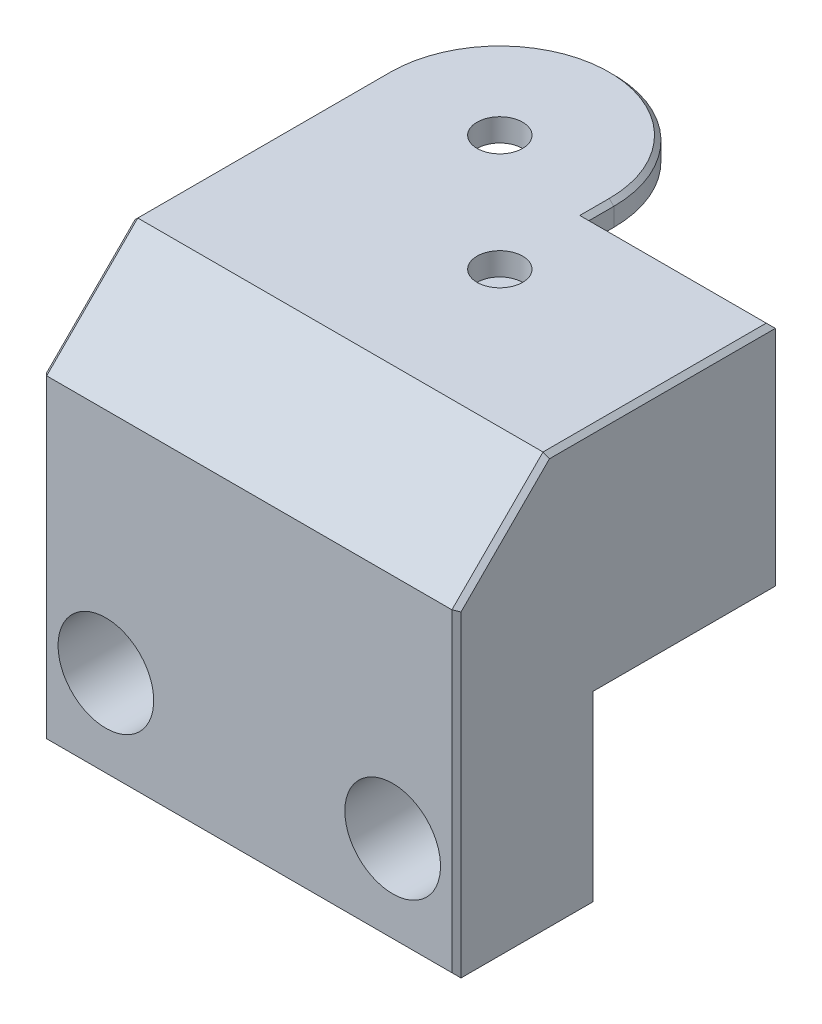
SolidWorks part; units mm, degrees
ref_plane "Front Plane" through (0, 0, 0) normal (0, 0, 1) x (1, 0, 0)
ref_plane "Top Plane" through (0, 0, 0) normal (0, 1, 0) x (1, 0, 0)
ref_plane "Right Plane" through (0, 0, 0) normal (1, 0, 0) x (0, 0, -1)
sketch "Sketch1" plane through (0, 0, 0) normal (0, 1, 0) x (1, 0, 0)
  line L0 (0, 0) -> (-20.24, 0) construction
  line L1 (20.24, -10) -> (25.24, -10)
  line L2 (-20.24, 10) -> (20.24, 10)
  line L3 (-20.24, 10) -> (-20.24, -10)
  line L4 (-20.24, -10) -> (20.24, -10)
  line L5 (20.24, 10) -> (20.24, -10) construction
  line L6 (-20.24, 10) -> (20.24, -10) construction
  line L7 (-20.24, -10) -> (20.24, 10) construction
  line L8 (25.24, -10) -> (25.24, 10)
  line L9 (25.24, 10) -> (20.24, 10)
  circle A0 centre (0, 0) radius 2.5
  point P3 (0, 0)
  dimension "D1" = 5
  dimension "D2" = 20
  dimension "D3" = 20.24
  dimension "D4" = 5
extrude "Boss-Extrude1" add sketch "Sketch1" along normal blind 25
sketch "Sketch9" plane through (0, 0, 10) normal (0, 0, 1) x (1, 0, 0)
  line L0 (25.24, 25) -> (25.24, 0) construction
  line L1 (-20.24, 25) -> (25.24, 25)
  line L2 (-20.24, 25) -> (-20.24, -20)
  line L3 (-20.24, -20) -> (25.24, -20)
  line L4 (25.24, 25) -> (25.24, -20)
  line L6 (-20.24, 0) -> (25.24, 0) construction
  dimension "D1" = 20
extrude "Boss-Extrude4" add sketch "Sketch9" along normal blind 15
sketch "Sketch10" plane through (0, 25, 0) normal (0, 1, 0) x (1, 0, 0)
  line L0 (10.16, 0) -> (10.16, 10)
  line L1 (25.24, 10) -> (-20.24, 10) construction
  line L2 (10.16, 10) -> (-10.16, 10)
  line L3 (-10.16, 10) -> (-10.16, 0)
  arc A0 (10.16, 0) -> (-10.16, 0) centre (0, 0) cw
  dimension "D1" = 10.16
extrude "Cut-Extrude2" cut sketch "Sketch10" against normal blind 19.5 from offset 2.5 offset against normal yes
sketch "Sketch14" plane through (0, 25, 0) normal (0, 1, 0) x (1, 0, 0)
  line L0 (464.5276, -6.3662) -> (0, -6.3662) construction
  line L1 (48.7314, 6.3662) -> (12.7324, 6.3662) construction
  line L2 (464.5276, -6.3662) -> (0, -6.3662)
  line L3 (48.7314, 6.3662) -> (12.7324, 6.3662)
  circle A0 centre (12.7324, 12.7324) radius 9.017 construction
  circle A1 centre (12.7324, 12.7324) radius 9.017
sketch "Sketch15" plane through (0, 25, 0) normal (0, 1, 0) x (1, 0, 0)
  line L0 (25.24, 10) -> (25.24, 12.7324)
  line L1 (0.2248, 12.7324) -> (0.2248, 10)
  line L2 (0.2248, 10) -> (25.24, 10)
  arc A0 (25.24, 12.7324) -> (0.2248, 12.7324) centre (12.7324, 12.7324) ccw
  circle A1 centre (12.7324, 12.7324) radius 2.5
  dimension "D1" = 5
extrude "Boss-Extrude5" add sketch "Sketch15" against normal up to surface (25 mm away) up to face at (2.5, 0, 0)
chamfer "Chamfer1" distance 10 angle 45 1 edges at (2.5, 25, 25)
ref_axis "Axis1" through (0, 3, 0) along (0, -1, 0)
ref_plane "Plane1" through (0, 0, 0) normal (-1, 0, 0) x (0, 0, 1)
sketch "Sketch16" plane through (25.24, 0, 0) normal (1, 0, 0) x (0, 0, -1)
  line L0 (-10.16, 22.5) -> (-10.16, 3) construction
  line L1 (-10.16, 3) -> (29.84, 3)
  line L2 (-10.16, 3) -> (-10.16, 22.5)
  line L3 (-10.16, 22.5) -> (29.84, 22.5)
  line L4 (29.84, 3) -> (29.84, 22.5)
  line L5 (2.5, 3) -> (-2.5, 3) construction
  line L6 (-2.5, 22.5) -> (2.5, 22.5) construction
  dimension "D1" = 40
extrude "Cut-Extrude3" cut sketch "Sketch16" against normal up to surface (25.24 mm away) up to plane "Plane1"
sketch "Sketch11" plane through (0, 0, 25) normal (0, 0, 1) x (1, 0, 0)
  line L0 (-20.24, -10) -> (25.24, -10) construction
  line L1 (25.24, -20) -> (25.24, 15) construction
  line L2 (-20.24, 15) -> (-20.24, -20) construction
  line L3 (-20.24, -20) -> (25.24, -20) construction
  circle A0 centre (-13.24, -10) radius 7
  circle A1 centre (18.24, -10) radius 7
  dimension "D2" = 14
  dimension "D1" = 10
sketch "Sketch17" plane through (0, 25, 0) normal (0, 1, 0) x (1, 0, 0)
  line L0 (0, 0) -> (10.16, 0) construction
  line L1 (10.16, 0) -> (25.24, 0) construction
  line L2 (25.24, -10.16) -> (25.24, 12.7324) construction
  line L3 (10.16, -3) -> (25.24, -3)
  line L4 (10.16, 3) -> (25.24, 3)
  line L5 (10.16, -3) -> (10.16, 3)
  line L6 (25.24, -3) -> (25.24, 3)
  dimension "D1" = 10.16
  dimension "D2" = 3
  dimension "D3" = 3
extrude "Boss-Extrude6" add sketch "Sketch17" against normal up to surface (22 mm away) up to face at (0, 3, -2.5)
hole_wizard "CBORE for M5 SBHCS1" positions "Sketch12" profile "Sketch13" counterbore size "M5" standard "ANSI Metric" end condition through all
sketch "Sketch12" plane through (0, 0, 25) normal (0, 0, 1) x (1, 0, 0)
  point P0 (-13.24, -10)
  point P3 (18.24, -10)
sketch "Sketch13" plane through (-13.24, -10, 25) normal (1, 0, 0) x (0, -1, 0)
  line L0 (0, 0) -> (0, 50.24)
  line L1 (0, 50.24) -> (2.75, 50.24)
  line L3 (2.75, 50.24) -> (2.75, 9.75)
  line L4 (2.75, 9.75) -> (5.25, 9.75)
  line L5 (5.25, 9.75) -> (5.25, 0)
  line L7 (5.25, 0) -> (0, 0)
  line L11 (0, -6.35) -> (0, 107.95) construction
  dimension "Thru Hole Dia." = 5.5
  dimension "Thru Hole Depth" = 50.24
  dimension "C'Bore Dia." = 10.5
  dimension "C'Bore Depth" = 9.75
mirror "Mirror1" about plane through (25.24, 25, 10) normal (-1, 0, 0) of bodies 109
delete or keep bodies "Body-Delete/Keep 1" type delete bodies bodies 109
chamfer "Chamfer2" distance 0.5 angle 45 10 edges at (25.24, 25, 1.1338) (37.7476, 25, -25.24) (50.2552, 25, -11.3662) (60.4876, 25, -10) (70.72, 25, 2.5) (25.24, 20, 20) (25.24, -2.5, 25) (47.98, -20, 25) (70.72, -2.5, 25) (70.72, 20, 20)
